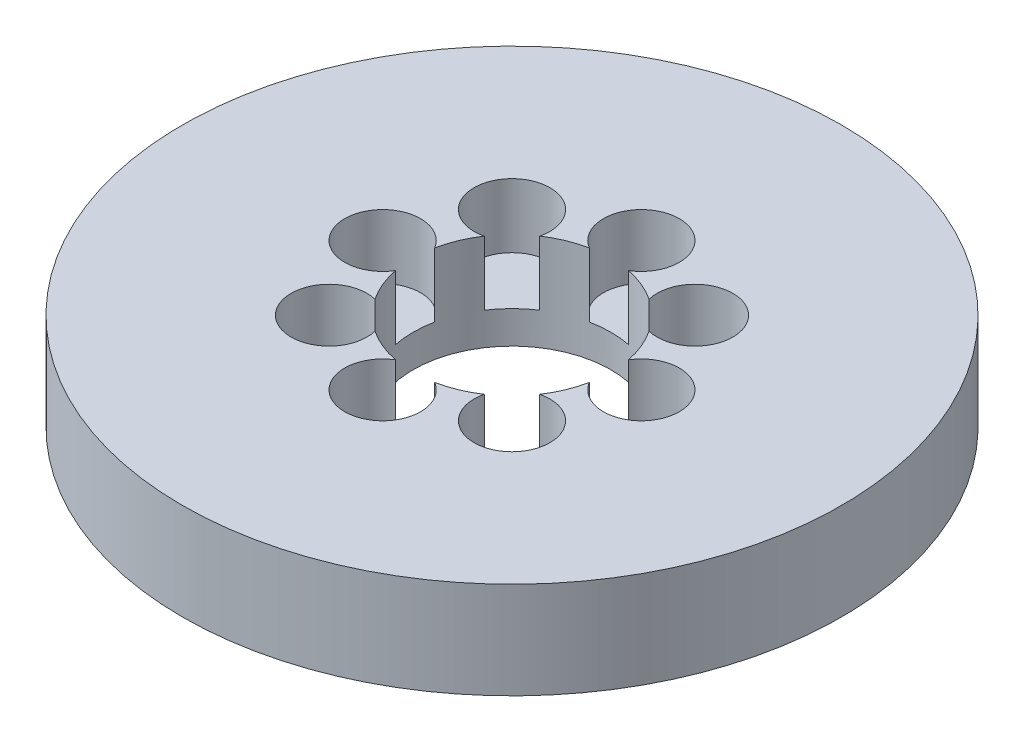
SolidWorks part; units mm, degrees
ref_plane "Front Plane" through (0, 0, 0) normal (0, 0, 1) x (1, 0, 0)
ref_plane "Top Plane" through (0, 0, 0) normal (0, 1, 0) x (1, 0, 0)
ref_plane "Right Plane" through (0, 0, 0) normal (1, 0, 0) x (0, 0, -1)
sketch "Sketch1" plane through (0, 0, 0) normal (0, 1, 0) x (1, 0, 0)
  circle A0 centre (0, 0) radius 75
  dimension "FLANGE_OD" = 150
extrude "Boss-Extrude1" add sketch "Sketch1" along normal blind 22
sketch "Sketch2" plane through (0, 0, 0) normal (0, 1, 0) x (1, 0, 0)
  circle A0 centre (0, 0) radius 22.5
  dimension "BORE_D" = 45
extrude "Cut-Extrude1" cut sketch "Sketch2" along normal through all
sketch "Sketch3" plane through (0, 22, 0) normal (0, 1, 0) x (1, 0, 0)
  circle A0 centre (0, 0) radius 29.4419 construction
  circle A1 centre (-29.4419, 0) radius 8.6316
  dimension "BOLT_D" = 17.2632
  dimension "BOLT_PCD" = 58.8837
extrude "Cut-Extrude2" cut sketch "Sketch3" against normal blind 14.6011
pattern_circular "CirPattern1" count 8 over 360 about axis through (0, 0, 0) along (0, 1, 0) of "Cut-Extrude2"
